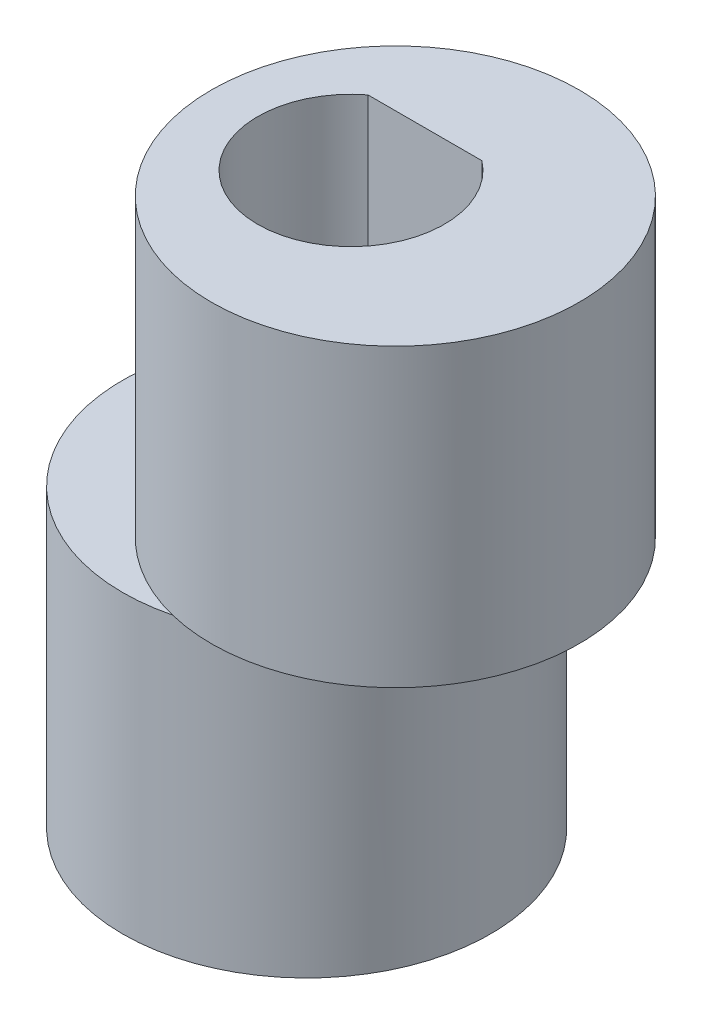
SolidWorks part; units mm, degrees
ref_plane "Front Plane" through (0, 0, 0) normal (0, 0, 1) x (1, 0, 0)
ref_plane "Top Plane" through (0, 0, 0) normal (0, 1, 0) x (1, 0, 0)
ref_plane "Right Plane" through (0, 0, 0) normal (1, 0, 0) x (0, 0, -1)
sketch "Sketch1" plane through (0, 0, 0) normal (0, 1, 0) x (1, 0, 0)
  line L0 (-2.4, 0) -> (0, 0)
  circle A0 centre (0, 0) radius 4.975
  circle A1 centre (-2.4, 0) radius 4.975
  circle A2 centre (-1.2, 0) radius 2.525
extrude "Boss-Extrude1" add sketch "Sketch1" along normal blind 8 contours A0
sketch "Sketch2" plane through (0, 0, 0) normal (0, 1, 0) x (1, 0, 0)
  circle A0 centre (-2.4, 0) radius 4.975
extrude "Boss-Extrude2" add sketch "Sketch2" against normal blind 8
sketch "Sketch4" plane through (0, 0, 0) normal (0, 1, 0) x (1, 0, 0)
  circle A0 centre (-1.2, 0) radius 2.525
extrude "Cut-Extrude1" cut sketch "Sketch4" against normal blind 8 and the other way blind 8
sketch "Sketch5" plane through (0, 8, 0) normal (0, 1, 0) x (1, 0, 0)
  line L1 (0.3413, 2) -> (-2.7413, 2)
  circle A0 centre (-1.2, 0) radius 2.525 construction
  arc A1 (-2.7413, 2) -> (0.3413, 2) centre (-1.2, 0) cw
extrude "Boss-Extrude3" add sketch "Sketch5" against normal blind 10 contours L1 region at (-1.2, 8, -2.212)
